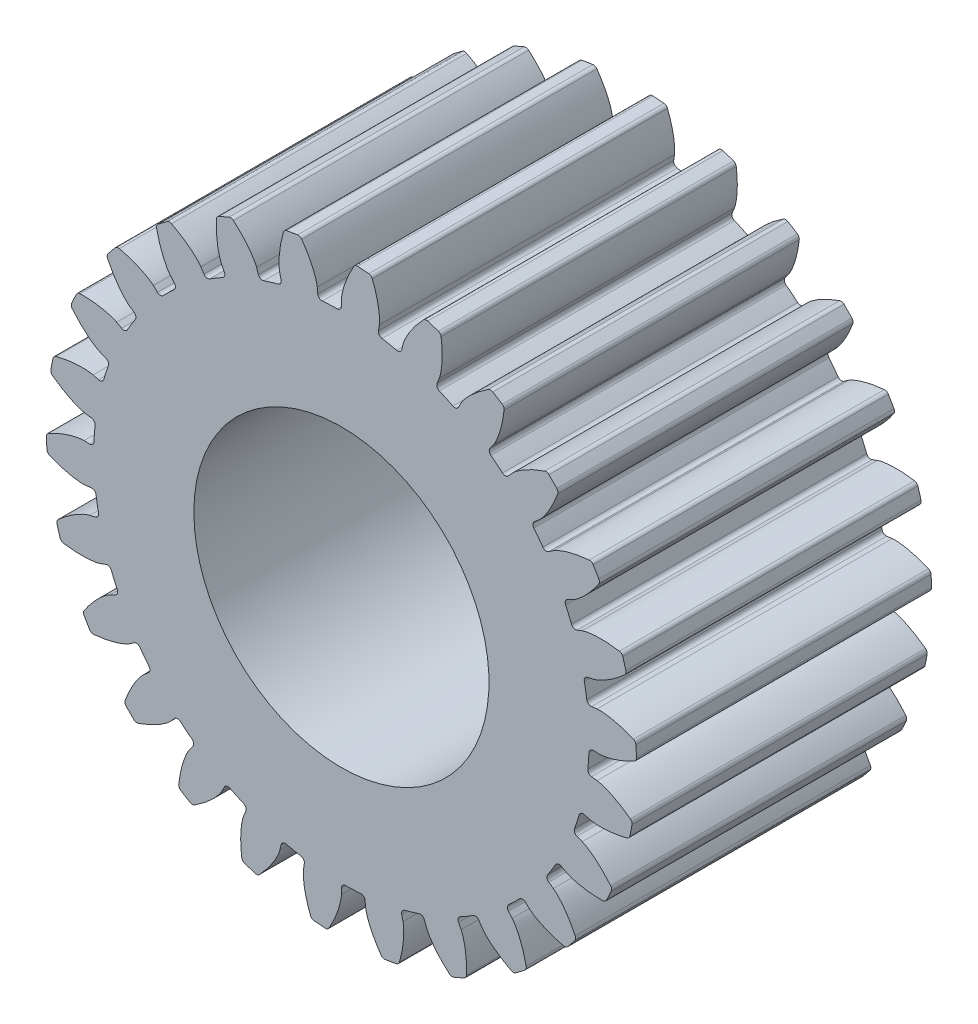
SolidWorks part; units mm, degrees
ref_plane "Front Plane" through (0, 0, 0) normal (0, 0, 1) x (1, 0, 0)
ref_plane "Top Plane" through (0, 0, 0) normal (0, 1, 0) x (1, 0, 0)
ref_plane "Right Plane" through (0, 0, 0) normal (1, 0, 0) x (0, 0, -1)
sketch "Involute Geometry" plane through (0, 0, 0) normal (0, 0, 1) x (1, 0, 0)
  line L0 (0, 12.216) -> (0, 0) construction
  line L1 (0, 0) -> (1.0333, 13.9618) construction
  line L2 (1.7984, 12.0829) -> (0, 0) construction
  line L3 (0.175, 12.9988) -> (0, 0) construction
  line L4 (0, 0) -> (1.7406, 12.883) construction
  circle A1 centre (0, 0) radius 12.216 construction
  circle A2 centre (0, 0) radius 13 construction
  circle A3 centre (0, 0) radius 14 construction
  circle A4 centre (0, 0) radius 11.75 construction
  arc A5 (0.6454, 13.9851) -> (1.4204, 13.9278) centre (0, 0) cw
  arc A6 (0.175, 12.9988) -> (1.7406, 12.883) centre (0, 0) cw construction
  spline S0 degree 4 poles (0, 12.216) (0, 12.2259) (0.0007, 12.2537) (0.0046, 12.3061) (0.0149, 12.3914) (0.0336, 12.4994) (0.064, 12.638) (0.108, 12.7997) (0.1647, 12.9755) (0.2354, 13.1642) (0.3138, 13.35) (0.3992, 13.5328) (0.4907, 13.7124) (0.6089, 13.9268) (0.7611, 14.1794) (0.9535, 14.4672) (1.1888, 14.7846) (1.4461, 15.0973) (1.7136, 15.3959) (1.9994, 15.6864) (2.287, 15.9594) (2.6008, 16.2305) (2.8982, 16.4744) (3.2472, 16.733) (3.5335, 16.9374) (3.9271, 17.1908) (4.1642, 17.3355) (4.4469, 17.4991) (4.5752, 17.5686) (4.654, 17.6115) knots 0 0 0 0 0 0.005377 0.015084 0.028532 0.04661 0.064855 0.092111 0.119476 0.146842 0.174209 0.201575 0.228941 0.256307 0.307035 0.361767 0.4165 0.471232 0.525964 0.580697 0.635429 0.690161 0.744894 0.799626 0.854358 0.909091 0.954545 1 1 1 1 1 construction
  spline S1 degree 4 poles (0, 12.216) (0, 12.2259) (0.0007, 12.2537) (0.0046, 12.3061) (0.0149, 12.3914) (0.0336, 12.4994) (0.064, 12.638) (0.108, 12.7997) (0.1647, 12.9755) (0.2354, 13.1642) (0.3138, 13.35) (0.3992, 13.5328) (0.4907, 13.7124) (0.6089, 13.9268) (0.7611, 14.1794) (0.9535, 14.4672) (1.1888, 14.7846) (1.4461, 15.0973) (1.7136, 15.3959) (1.9994, 15.6864) (2.287, 15.9594) (2.6008, 16.2305) (2.8982, 16.4744) (3.2472, 16.733) (3.5335, 16.9374) (3.8418, 17.1359) (3.9936, 17.2306) (4.0719, 17.2782) knots 0 0 0 0 0 0.005377 0.015084 0.028532 0.04661 0.064855 0.092111 0.119476 0.146842 0.174209 0.201575 0.228941 0.256307 0.307035 0.361767 0.4165 0.471232 0.525964 0.580697 0.635429 0.690161 0.744894 0.799626 0.854358 0.909091 0.909091 0.909091 0.909091 0.909091
  spline S3 degree 4 poles (1.7984, 12.0829) (1.7999, 12.0927) (1.8033, 12.1203) (1.8071, 12.1727) (1.8095, 12.2586) (1.8069, 12.3682) (1.7972, 12.5097) (1.7775, 12.6762) (1.7473, 12.8584) (1.7051, 13.0554) (1.655, 13.2507) (1.5974, 13.4441) (1.5334, 13.6352) (1.448, 13.8647) (1.3347, 14.1369) (1.1867, 14.45) (1.0007, 14.7985) (0.7922, 15.1457) (0.5716, 15.4804) (0.3317, 15.8098) (0.0874, 16.1222) (-0.1831, 16.4365) (-0.4413, 16.7215) (-0.7484, 17.0287) (-1.0015, 17.2731) (-1.3535, 17.5817) (-1.5667, 17.7597) (-1.8223, 17.9631) (-1.9389, 18.0507) (-2.0106, 18.1047) knots 0 0 0 0 0 0.005377 0.015084 0.028532 0.04661 0.064855 0.092111 0.119476 0.146842 0.174209 0.201575 0.228941 0.256307 0.307035 0.361767 0.4165 0.471232 0.525964 0.580697 0.635429 0.690161 0.744894 0.799626 0.854358 0.909091 0.954545 1 1 1 1 1 construction
  spline S4 degree 4 poles (1.7984, 12.0829) (1.7999, 12.0927) (1.8033, 12.1203) (1.8071, 12.1727) (1.8095, 12.2586) (1.8069, 12.3682) (1.7972, 12.5097) (1.7775, 12.6762) (1.7473, 12.8584) (1.7051, 13.0554) (1.655, 13.2507) (1.5974, 13.4441) (1.5334, 13.6352) (1.448, 13.8647) (1.3347, 14.1369) (1.1867, 14.45) (1.0007, 14.7985) (0.7922, 15.1457) (0.5716, 15.4804) (0.3317, 15.8098) (0.0874, 16.1222) (-0.1831, 16.4365) (-0.4413, 16.7215) (-0.7484, 17.0287) (-1.0015, 17.2731) (-1.2772, 17.5148) (-1.4134, 17.6308) (-1.4839, 17.6894) knots 0 0 0 0 0 0.005377 0.015084 0.028532 0.04661 0.064855 0.092111 0.119476 0.146842 0.174209 0.201575 0.228941 0.256307 0.307035 0.361767 0.4165 0.471232 0.525964 0.580697 0.635429 0.690161 0.744894 0.799626 0.854358 0.909091 0.909091 0.909091 0.909091 0.909091
  dimension "D5" = 6.923
sketch "Sketch2" plane through (0, 0, 0) normal (0, 0, 1) x (1, 0, 0)
  circle A0 centre (0, 0) radius 11.75 construction
  circle A1 centre (0, 0) radius 11.75
extrude "Boss-Extrude1" add sketch "Sketch2" along normal mid plane 14
sketch "Sketch3" plane through (0, 0, 0) normal (0, 0, 1) x (1, 0, 0)
  line L0 (0, 12.216) -> (0, 0) construction
  line L1 (1.7984, 12.0829) -> (0, 0) construction
  line L2 (0, 12.216) -> (0, 11.75)
  line L4 (1.7984, 12.0829) -> (1.7298, 11.622)
  circle A1 centre (0, 0) radius 11.75 construction
  arc A3 (0, 11.75) -> (1.7298, 11.622) centre (0, 0) cw
  arc A4 (1.4204, 13.9278) -> (0.6454, 13.9851) centre (0, 0) ccw construction
  arc A5 (1.4204, 13.9278) -> (0.6454, 13.9851) centre (0, 0) ccw
  spline S0 degree 4 poles (999.8581, 25.2356) (18.0155, 10.2173) (0.3577, 10.7107) (-0.0848, 11.5636) (0.0149, 12.3914) (0.0336, 12.4994) (0.064, 12.638) (0.108, 12.7997) (0.1647, 12.9755) (0.2354, 13.1642) (0.3138, 13.35) (0.3992, 13.5328) (0.4907, 13.7124) (0.6089, 13.9268) (0.7611, 14.1794) (0.9535, 14.4672) (1.1888, 14.7846) (1.4461, 15.0973) (1.7136, 15.3959) (1.9994, 15.6864) (2.287, 15.9594) (2.6008, 16.2305) (2.8982, 16.4744) (3.2472, 16.733) (4.4419, 17.5861) (8.1221, 19.6216) (-23.9178, -0.2396) (859.2438, 535.5339) knots -0.405932 -0.405932 -0.405932 -0.405932 -0.405932 0.005377 0.015084 0.028532 0.04661 0.064855 0.092111 0.119476 0.146842 0.174209 0.201575 0.228941 0.256307 0.307035 0.361767 0.4165 0.471232 0.525964 0.580697 0.635429 0.690161 0.744894 0.799626 0.854358 1.603617 1.603617 1.603617 1.603617 1.603617 only from (0, 12.216) to (3.8711, 11.595) construction
  spline S1 degree 4 poles (0, 12.216) (0, 12.2259) (0.0007, 12.2537) (0.0046, 12.3061) (0.0149, 12.3914) (0.0336, 12.4994) (0.064, 12.638) (0.108, 12.7997) (0.1647, 12.9755) (0.2354, 13.1642) (0.3138, 13.35) (0.3992, 13.5328) (0.4919, 13.7149) (0.5664, 13.8498) (0.6183, 13.9394) (0.6454, 13.9851) knots 0 0 0 0 0 0.005377 0.015084 0.028532 0.04661 0.064855 0.092111 0.119476 0.146842 0.174209 0.201575 0.228941 0.257808 0.257808 0.257808 0.257808 0.257808
  spline S3 degree 4 poles (-985.2487, 172.157) (-16.315, 12.7581) (1.223, 10.6467) (1.7863, 11.4251) (1.8095, 12.2586) (1.8069, 12.3682) (1.7972, 12.5097) (1.7775, 12.6762) (1.7473, 12.8584) (1.7051, 13.0554) (1.655, 13.2507) (1.5974, 13.4441) (1.5334, 13.6352) (1.448, 13.8647) (1.3347, 14.1369) (1.1867, 14.45) (1.0007, 14.7985) (0.7922, 15.1457) (0.5716, 15.4804) (0.3317, 15.8098) (0.0874, 16.1222) (-0.1831, 16.4365) (-0.4413, 16.7215) (-0.7484, 17.0287) (-1.8045, 18.0484) (-5.1449, 20.6035) (23.6219, -3.7581) (-771.0418, 656.1943) knots -0.405932 -0.405932 -0.405932 -0.405932 -0.405932 0.005377 0.015084 0.028532 0.04661 0.064855 0.092111 0.119476 0.146842 0.174209 0.201575 0.228941 0.256307 0.307035 0.361767 0.4165 0.471232 0.525964 0.580697 0.635429 0.690161 0.744894 0.799626 0.854358 1.603617 1.603617 1.603617 1.603617 1.603617 only from (1.7984, 12.0829) to (-1.4839, 17.6894) construction
  spline S4 degree 4 poles (1.7984, 12.0829) (1.7999, 12.0927) (1.8033, 12.1203) (1.8071, 12.1727) (1.8095, 12.2586) (1.8069, 12.3682) (1.7972, 12.5097) (1.7775, 12.6762) (1.7473, 12.8584) (1.7051, 13.0554) (1.655, 13.2507) (1.5974, 13.4441) (1.5325, 13.6379) (1.4787, 13.7823) (1.4405, 13.8785) (1.4204, 13.9278) knots 0 0 0 0 0 0.005377 0.015084 0.028532 0.04661 0.064855 0.092111 0.119476 0.146842 0.174209 0.201575 0.228941 0.257808 0.257808 0.257808 0.257808 0.257808
extrude "Boss-Extrude2" add sketch "Sketch3" along normal through all and the other way through all
fillet "Fillet2" [suppressed] radius 0.381
pattern_circular "CirPattern1" count 26 over 360 about axis through (0, 0, 7) along (0, 0, -1) of "Boss-Extrude2", "Fillet2"
ref_axis "Axis1" through (0, 0, 7) along (0, 0, -1)
sketch "Sketch4" plane through (0, 0, -7) normal (0, 0, -1) x (-1, 0, 0)
  circle A1 centre (0, 0) radius 7
  dimension "D1" = 14
extrude "Cut-Extrude1" cut sketch "Sketch4" against normal through all
fillet "Fillet3" radius 0.2 104 edges at (-8.5821, 8.0256, 0) (-9.6701, 6.6748, 0) (-10.9864, 4.1666, 0) (-11.3287, 3.1181, 0) (-11.6643, 1.4163, 0) (-11.7457, 0.3163, 0) (-11.6643, -1.4163, 0) (-11.4801, -2.5038, 0) (-10.9864, -4.1666, 0) (-10.5473, -5.1784, 0) (-9.6701, -6.6748, 0) (-9.0016, -7.5521, 0) (-7.7917, -8.795, 0) (-6.9327, -9.4869, 0) (-5.4605, -10.4041, 0) (-4.4609, -10.8703, 0) (-2.812, -11.4086, 0) (-1.7298, -11.622, 0) (0, -11.75, 0) (1.1018, -11.6982, 0) (2.812, -11.4086, 0) (3.8693, -11.0946, 0) (5.4605, -10.4041, 0) (6.412, -9.8462, 0) (7.7917, -8.795, 0) (8.5821, -8.0256, 0) (9.6701, -6.6748, 0) (10.2533, -5.7386, 0) (10.9864, -4.1666, 0) (11.3287, -3.1181, 0) (11.6643, -1.4163, 0) (11.7457, -0.3163, 0) (11.6643, 1.4163, 0) (11.4801, 2.5038, 0) (10.9864, 4.1666, 0) (10.5473, 5.1784, 0) (9.6701, 6.6748, 0) (9.0016, 7.5521, 0) (7.7917, 8.795, 0) (6.9327, 9.4869, 0) (5.4605, 10.4041, 0) (4.4609, 10.8703, 0) (2.812, 11.4086, 0) (1.7298, 11.622, 0) (0, 11.75, 0) (-10.2533, 5.7386, 0) (-1.1018, 11.6982, 0) (-2.812, 11.4086, 0) (-3.8693, 11.0946, 0) (-5.4605, 10.4041, 0) (-6.412, 9.8462, 0) (-7.7917, 8.795, 0) (1.4204, 13.9278, 0) (3.9735, 13.4243, 0) (4.7123, 13.1831, 0) (7.0707, 12.0833, 0) (7.7303, 11.6723, 0) (9.757, 10.04, 0) (10.299, 9.4831, 0) (11.8762, 7.4133, 0) (12.2692, 6.7429, 0) (13.3052, 4.3557, 0) (13.5264, 3.6107, 0) (13.9609, 1.045, 0) (13.9974, 0.2687, 0) (13.8053, -2.3265, 0) (13.655, -3.0889, 0) (12.8474, -5.5627, 0) (12.519, -6.267, 0) (11.1429, -8.4756, 0) (10.6554, -9.0809, 0) (8.7907, -10.896, 0) (8.1726, -11.367, 0) (5.9277, -12.6832, 0) (5.2148, -12.9925, 0) (2.7202, -13.7332, 0) (1.954, -13.863, 0) (-0.6454, -13.9851, 0) (-1.4204, -13.9278, 0) (-3.9735, -13.4243, 0) (-4.7123, -13.1831, 0) (-7.0707, -12.0833, 0) (-7.7303, -11.6723, 0) (-9.757, -10.04, 0) (-10.299, -9.4831, 0) (-11.8762, -7.4133, 0) (-12.2692, -6.7429, 0) (-13.3052, -4.3557, 0) (-13.5264, -3.6107, 0) (-13.9609, -1.045, 0) (-13.9974, -0.2687, 0) (-13.8053, 2.3265, 0) (-13.655, 3.0889, 0) (-12.8474, 5.5627, 0) (-12.519, 6.267, 0) (-11.1429, 8.4756, 0) (-10.6554, 9.0809, 0) (-8.7907, 10.896, 0) (-8.1726, 11.367, 0) (-5.9277, 12.6832, 0) (-5.2148, 12.9925, 0) (-2.7202, 13.7332, 0) (-1.954, 13.863, 0) (0.6454, 13.9851, 0)
equation "\"N\"= 26'Number of Teeth"
equation "\"m\"= 1mm'Diametral Pitch"
equation "\"phi\"= 20deg'Pressure Angle"
equation "\"a\"= \"m\"'Addendum"
equation "\"b\"= 1.25 * \"m\"'Dedendum"
equation "\"Dp\"= \"N\" * \"m\"'Pitch diameter"
equation "\"Db\"= \"Dp\" * cos ( \"phi\" )'Base diameter"
equation "\"D1@Involute Geometry\" = \"Db\""
equation "\"D2@Involute Geometry\" = \"Dp\""
equation "\"D3@Involute Geometry\" = \"Dp\" + 2 * \"a\""
equation "\"D4@Involute Geometry\" = \"Dp\" - 2 * \"b\""
equation "\"D1@CirPattern1\"=\"N\""
equation "\"D5@Involute Geometry\"=180/\"N\""
equation "\"D1@Boss-Extrude1\"=14*\"m\""
equation "\"alpha\"= sqr ( \"Dp\" ^ 2 - \"Db\" ^ 2 ) / \"Db\" * 180 / pi - \"phi\""
equation "\"beta\"= ( ( 360deg / \"N\" ) / 4 - \"alpha\" )"
